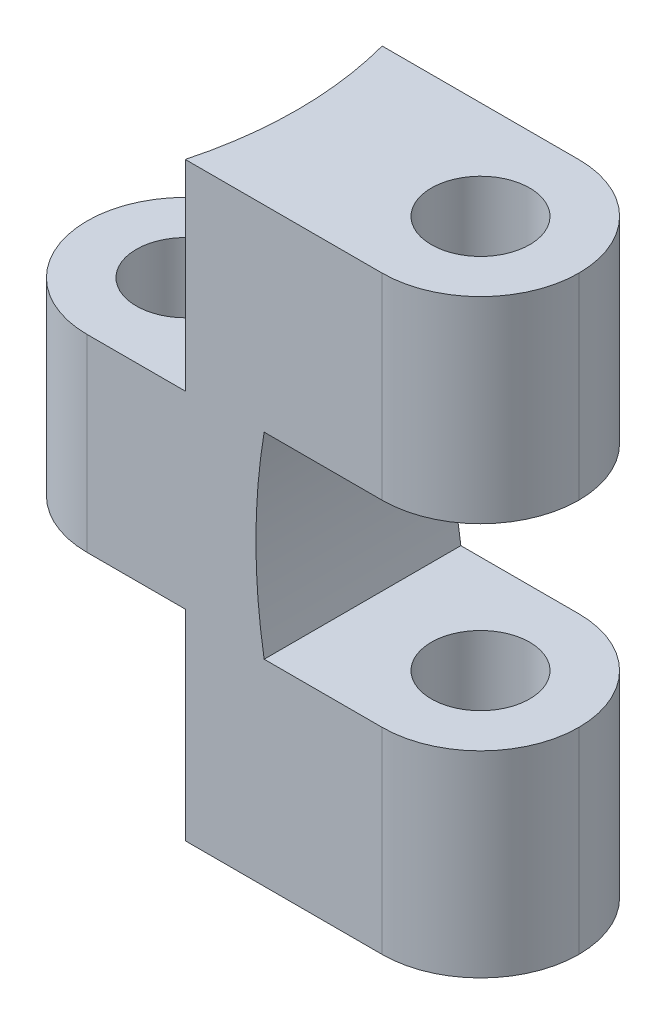
SolidWorks part; units mm, degrees
ref_plane "Plano frontal" through (0, 0, 0) normal (0, 0, 1) x (1, 0, 0)
ref_plane "Plano superior" through (0, 0, 0) normal (0, 1, 0) x (1, 0, 0)
ref_plane "Plano direito" through (0, 0, 0) normal (1, 0, 0) x (0, 0, -1)
sketch "Esboço1" plane through (0, 0, 0) normal (0, 0, 1) x (1, 0, 0)
  line L0 (20, 15) -> (-20, -15) construction
  line L1 (-10, 15) -> (20, 15)
  line L2 (-20, 4.8) -> (-20, -4.8)
  line L3 (-10, -15) -> (20, -15)
  line L4 (20, 15) -> (20, -15)
  line L5 (-10, 15) -> (-10, 4.8)
  line L6 (-20, 4.8) -> (-10, 4.8)
  line L7 (-20, 4.8) -> (-20, -4.8)
  line L8 (-20, -4.8) -> (-10, -4.8)
  line L10 (-10, -4.8) -> (-10, -15)
  dimension "D2" = 40
  dimension "D3" = 10.2
  dimension "D4" = 10.2
  dimension "D5" = 10
extrude "Ressalto-extrusão1" add sketch "Esboço1" along normal blind 10 contours L0 L1 L5 L6 L2 L8 L10 | L4 L0 L10 L3 region at (8, -4.5, 0) region at (-3.3218, 5.8391, 0)
sketch "Esboço2" plane through (0, -4.8, 0) normal (0, -1, 0) x (1, 0, 0)
  circle A0 centre (-15, 5) radius 2.5
  dimension "D1" = 5
extrude "Corte-extrusão1" cut sketch "Esboço2" against normal blind 10
fillet "Filete1" radius 5 2 edges at (-20, 0, 0) (-20, 0, 10)
sketch "Esboço5" plane through (0, -15, 0) normal (0, -1, 0) x (1, 0, 0)
  line L0 (-10, 10) -> (-10, 0)
  arc A0 (-10, 10) -> (-10, 0) centre (-28.6603, 5) cw
extrude "Corte-extrusão4" cut sketch "Esboço5" against normal blind 10
sketch "Esboço6" plane through (0, 15, 0) normal (0, 1, 0) x (1, 0, 0)
  line L0 (-10, -10) -> (-10, 0) construction
  line L1 (-10, -9.9505) -> (-10, 0)
  arc A0 (-10, 0) -> (-10, -9.9505) centre (-28.568, -4.9753) cw
extrude "Corte-extrusão5" cut sketch "Esboço6" against normal blind 10
sketch "Esboço7" plane through (0, 15, 0) normal (0, 1, 0) x (1, 0, 0)
  line L0 (-10, -10) -> (20, -10) construction
  line L1 (20, 0) -> (5, 0)
  line L2 (20, 0) -> (20, -10)
  line L3 (20, -10) -> (5, -10)
  line L4 (5, 0) -> (5, -10)
  dimension "D1" = 15
extrude "Corte-extrusão6" cut sketch "Esboço7" against normal up to next
sketch "Esboço8" plane through (0, 0, 10) normal (0, 0, 1) x (1, 0, 0)
  line L0 (5, -15) -> (5, 15) construction
  line L1 (-6, 5) -> (5, 5)
  line L2 (-6, 5) -> (-6, -5)
  line L3 (-6, -5) -> (5, -5)
  line L4 (5, 5) -> (5, -5)
  line L5 (-10, 15) -> (5, 15) construction
  line L6 (-10, -15) -> (5, -15) construction
  dimension "D1" = 10
  dimension "D2" = 10
  dimension "D3" = 11
extrude "Corte-extrusão7" cut sketch "Esboço8" against normal through all
sketch "Esboço9" plane through (0, 0, 0) normal (0, 0, -1) x (-1, 0, 0)
  line L0 (6, -5) -> (6, 5)
  arc A0 (6, 5) -> (6, -5) centre (-23.5804, 0) cw
extrude "Corte-extrusão8" cut sketch "Esboço9" against normal blind 20
sketch "Esboço10" plane through (0, 15, 0) normal (0, 1, 0) x (1, 0, 0)
  line L0 (5, 0) -> (5, -10) construction
  line L1 (-10, -10) -> (5, -10) construction
  circle A0 centre (0, -5) radius 2.5
  dimension "D3" = 5
  dimension "D1" = 5
  dimension "D2" = 5
extrude "Corte-extrusão9" cut sketch "Esboço10" against normal up to surface (30 mm away) up to face at (-2.3354, -15, 5)
fillet "Filete2" radius 5 4 edges at (5, -10, 0) (5, -10, 10) (5, 10, 10) (5, 10, 0)
